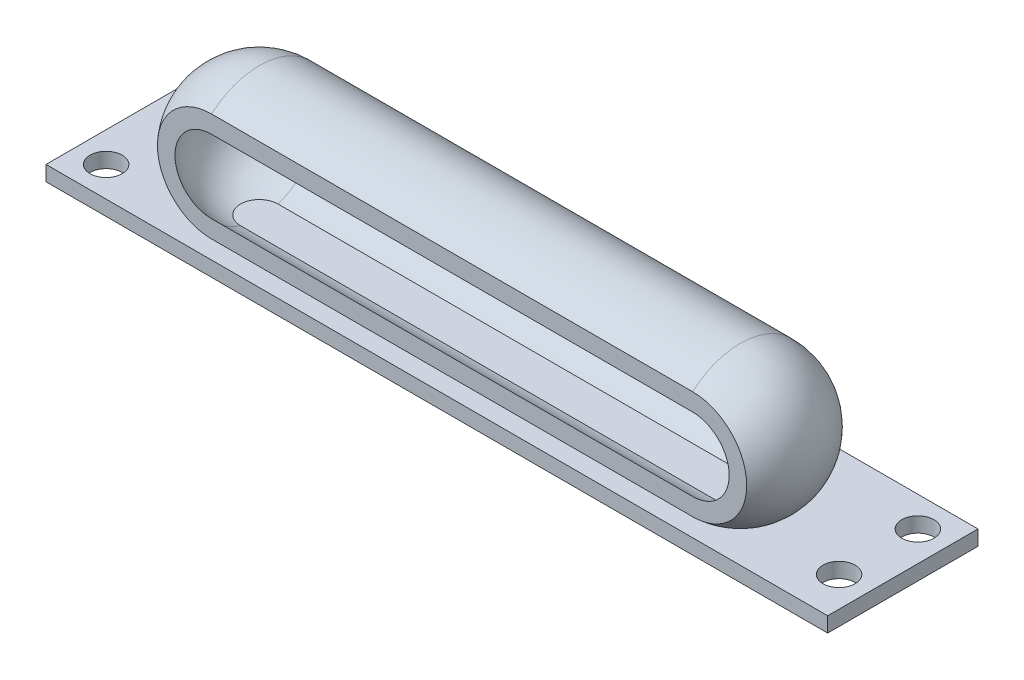
SolidWorks part; units mm, degrees
ref_plane "Front Plane" through (0, 0, 0) normal (0, 0, 1) x (1, 0, 0)
ref_plane "Top Plane" through (0, 0, 0) normal (0, 1, 0) x (1, 0, 0)
ref_plane "Right Plane" through (0, 0, 0) normal (1, 0, 0) x (0, 0, -1)
sketch "Sketch1" plane through (0, 0, 0) normal (0, 0, 1) x (1, 0, 0)
  line L0 (0, 0) -> (50.8, 0) construction
  line L1 (0, 7.62) -> (50.8, 7.62)
  line L3 (-7.62, 0) -> (58.42, 0)
  arc A0 (0, 7.62) -> (-7.62, 0) centre (0, 0) ccw
  arc A1 (58.42, 0) -> (50.8, 7.62) centre (50.8, 0) ccw
  point P3 (25.4, 0)
  dimension "D2" = 7.62
  dimension "D4" = 7.62
  dimension "D1" = 50.8
  dimension "D3" = 66.04
revolve "Revolve1" add sketch "Sketch1" angle 360 about L0
sketch "Sketch2" plane through (0, 0, 0) normal (1, 0, 0) x (0, 0, -1)
  line L0 (-5.0402, 5.715) -> (-5.0402, -5.715)
  line L1 (-5.0402, -5.715) -> (-10.1202, -5.715)
  line L2 (-10.1202, -5.715) -> (-10.1202, 5.715)
  line L3 (-10.1202, 5.715) -> (-5.0402, 5.715)
  circle A0 centre (0, 0) radius 7.62 construction
  dimension "D1" = 11.43
  dimension "D2" = 5.08
extrude "Cut-Extrude1" cut sketch "Sketch2" against normal mid plane 152.4
shell "Shell1" thickness 1.27 removed face at (25.4, 0, 5.0402)
ref_plane "Plane1" through (0, -7.62, 0) normal (0, 1, 0) x (1, 0, 0)
sketch "Sketch3" plane through (0, -7.62, 0) normal (0, 1, 0) x (1, 0, 0)
  line L0 (0, -5.0402) -> (50.8, -5.0402) construction
  line L1 (-15.875, 9.2274) -> (66.675, 9.2274)
  line L2 (-15.875, 9.2274) -> (-15.875, -6.6476)
  line L3 (-15.875, -6.6476) -> (66.675, -6.6476)
  line L4 (66.675, 9.2274) -> (66.675, -6.6476)
  line L5 (50.8, 7.62) -> (50.8, -5.0402) construction
  point P4 (-15.875, 1.2899)
  point P6 (25.4, -6.6476)
  point P9 (25.4, -5.0402)
  point P12 (50.8, 1.2899)
  dimension "D1" = 15.875
  dimension "D2" = 82.55
extrude "Boss-Extrude1" add sketch "Sketch3" along normal blind 1.5875
sketch "Sketch4" plane through (0, -6.0325, 0) normal (0, 1, 0) x (1, 0, 0)
  line L0 (66.675, 9.2274) -> (-15.875, 9.2274) construction
  line L1 (66.675, -6.6476) -> (66.675, 9.2274) construction
  line L2 (-15.875, 9.2274) -> (-15.875, -6.6476) construction
  line L3 (-15.875, -6.6476) -> (66.675, -6.6476) construction
  point P0 (-12.7, 6.0524)
  point P1 (-12.7, -3.4726)
  point P2 (63.5, 6.0524)
  point P3 (63.5, -2.2692)
  point P8 (0, 0)
  point P9 (0, 0)
  point P10 (0, 0)
  dimension "D1" = 3.175
  dimension "D2" = 3.175
  dimension "D3" = 3.175
  dimension "D4" = 3.175
hole_wizard "M3 Clearance Hole1" positions "Sketch5" profile "Sketch6" hole size "M3" standard "ANSI Metric" end condition through all
sketch "Sketch5" plane through (0, -6.0325, 0) normal (0, 1, 0) x (1, 0, 0)
  point P0 (-12.7, 6.0524)
  point P3 (-12.7, -3.4726)
  point P6 (63.5, 6.0524)
  point P9 (63.5, -2.2692)
sketch "Sketch6" plane through (-12.7, -6.0325, -6.0524) normal (1, 0, 0) x (0, 0, 1)
  line L0 (0, 0) -> (0, 1.5875)
  line L1 (0, 1.5875) -> (1.7, 1.5875)
  line L2 (1.7, 1.5875) -> (1.7, 0)
  line L5 (1.7, 0) -> (0, 0)
  line L11 (0, -6.35) -> (0, 107.95) construction
  dimension "Thru Hole Dia." = 3.4
  dimension "Thru Hole Depth" = 1.5875
